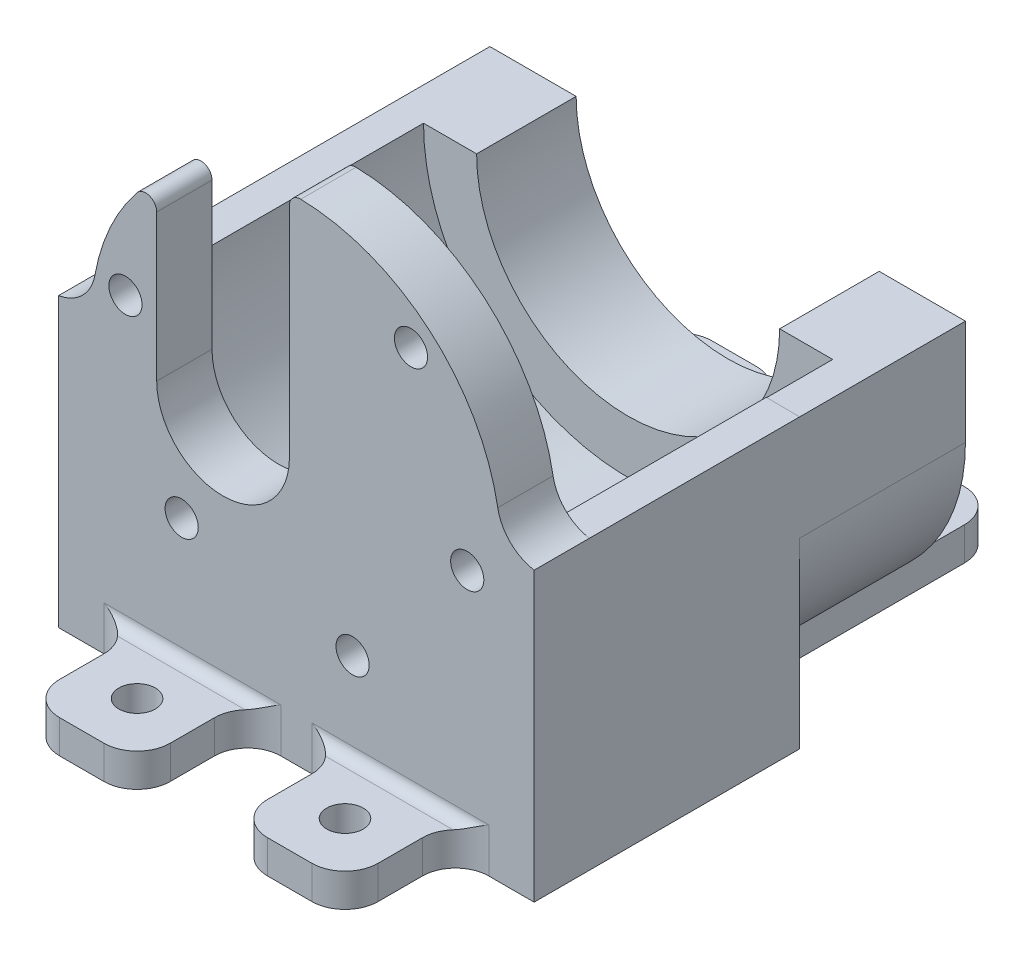
SolidWorks part; units mm, degrees
ref_plane "Front Plane" through (0, 0, 0) normal (0, 0, 1) x (1, 0, 0)
ref_plane "Top Plane" through (0, 0, 0) normal (0, 1, 0) x (1, 0, 0)
ref_plane "Right Plane" through (0, 0, 0) normal (1, 0, 0) x (0, 0, -1)
sketch "Sketch1" plane through (0, 0, 0) normal (0, 0, 1) x (1, 0, 0)
  line L0 (13.7, 13) -> (21.5, 13)
  line L3 (-21.5, 13) -> (-13.7, 13)
  line L4 (-21.5, 13) -> (-21.5, -13)
  line L5 (-21.5, -13) -> (21.5, -13)
  line L6 (21.5, 13) -> (21.5, -13)
  line L7 (-21.5, 13) -> (21.5, -13) construction
  line L8 (-21.5, -13) -> (21.5, 13) construction
  arc A0 (-13.7, 13) -> (13.7, 13) centre (0, 13) ccw
  point P0 (0, 0)
  dimension "D2" = 27.4
  dimension "D1" = 26
  dimension "43" = 43
  dimension "D3" = 7.8
  dimension "D4" = 7.8
extrude "Boss-Extrude1" add sketch "Sketch1" along normal blind 9
sketch "Sketch2" plane through (0, 0, 9) normal (0, 0, 1) x (1, 0, 0)
  line L0 (18.5, 13) -> (21.5, 13)
  line L2 (-21.5, 13) -> (-18.5, 13)
  line L3 (-21.5, 13) -> (-21.5, -13)
  line L4 (-21.5, -13) -> (21.5, -13)
  line L5 (21.5, 13) -> (21.5, -13)
  line L6 (-21.5, 13) -> (21.5, -13) construction
  line L7 (-21.5, -13) -> (21.5, 13) construction
  arc A0 (-18.5, 13) -> (18.5, 13) centre (0, 13) ccw
  point P1 (0, 0)
  dimension "D1" = 43
  dimension "37" = 37
  dimension "D2" = 26
  dimension "D3" = 3
  dimension "26" = 26
extrude "Boss-Extrude2" add sketch "Sketch2" along normal blind 25 contours L2 A0 L0 L5 L4 L3
fillet "Fillet1" radius 16.5 2 edges at (-21.5, -13, 17) (21.5, -13, 17)
sketch "Sketch4" plane through (0, 0, 0) normal (0, 0, -1) x (-1, 0, 0)
  line L0 (-21.5, 3.5) -> (-21.5, 13) construction
  line L1 (-21.5, 13) -> (-13.7, 13) construction
  line L2 (-14.4, -10) -> (-4.4, -10)
  line L3 (-14.4, -10) -> (-14.4, -13)
  line L4 (-14.4, -13) -> (-4.4, -13)
  line L5 (-4.4, -10) -> (-4.4, -13)
  line L7 (0, -15.2464) -> (0, 14.7255) construction
  line L8 (14.4, -13) -> (4.4, -13)
  line L9 (4.4, -10) -> (4.4, -13)
  line L10 (14.4, -10) -> (4.4, -10)
  line L11 (14.4, -10) -> (14.4, -13)
  dimension "D1" = 3
  dimension "10" = 10
  dimension "D2" = 17.1
  dimension "D3" = 23
extrude "Boss-Extrude3" add sketch "Sketch4" along normal blind 10 and the other way up to surface (34 mm away) other way up to face at (0, 0.9582, 34)
sketch "Sketch5" plane through (0, -10, 0) normal (0, 1, 0) x (1, 0, 0)
  line L0 (14.4, 0) -> (14.4, 10) construction
  line L2 (4.4, 10) -> (14.4, 10) construction
  line L3 (0, 16.1678) -> (0, -19.3517) construction
  circle A0 centre (9.4, 5) radius 1.65
  circle A1 centre (-9.4, 5) radius 1.65
  dimension "D1" = 3.3
  dimension "D2" = 5
  dimension "D3" = 5
extrude "Cut-Extrude1" cut sketch "Sketch5" against normal up to surface (3 mm away) up to face at (0, -13, 3.5)
fillet "Fillet2" radius 3 8 edges at (-4.4, -11.5, 0) (4.4, -11.5, 0) (9.4, -10, 0) (14.4, -11.5, -10) (4.4, -11.5, -10) (-9.4, -10, 0) (-4.4, -11.5, -10) (-14.4, -11.5, -10)
sketch "Sketch12" plane through (0, 0, 34) normal (0, 0, 1) x (1, 0, 0)
  line L0 (-14.4, -13) -> (14.4, -13) construction
  line L5 (-21.5, 13) -> (-21.5, 3.5) construction
  line L6 (-13.7, 13) -> (-18.5, 13) construction
  circle A0 centre (0, 13) radius 18.5
  circle A1 centre (0, 13) radius 15.75 construction
  circle A2 centre (-15.4519, 16.05) radius 1.5
  circle A3 centre (-5.0846, 27.9067) radius 1.5
  circle A4 centre (10.3673, 24.8567) radius 1.5
  circle A5 centre (15.4519, 9.95) radius 1.5
  circle A6 centre (5.0846, -1.9067) radius 1.5
  circle A7 centre (-10.3673, 1.1433) radius 1.5
  circle A8 centre (-6.6251, 10.74) radius 6
  dimension "D3" = 37
  dimension "D4" = 31.5
  dimension "D5" = 3
  dimension "D6" = 21.5
  dimension "D8" = 12
  dimension "D9" = 3.05
  dimension "D10" = 7
  dimension "D2" = 26
  dimension "D7" = 6
extrude "Boss-Extrude8" add sketch "Sketch12" along normal blind 5 separate body
sketch "Sketch13" plane through (0, 0, 34) normal (0, 0, 1) x (1, 0, 0)
  line L0 (-21.5, 13) -> (-18.5, 13) construction
  line L2 (-21.5, 13) -> (-21.5, -13)
  line L3 (-21.5, -13) -> (21.5, -13)
  line L4 (21.5, 13) -> (21.5, -13)
  line L5 (-18.5, 13) -> (-21.5, 13)
  line L6 (18.5, 13) -> (18.4962, 13.0344)
  line L7 (18.4962, 13.0344) -> (21.5, 13)
  arc A0 (18.5, 13) -> (-18.5, 13) centre (0, 13) cw
  arc A1 (-18.5, 13) -> (18.5, 13) centre (0, 13) ccw construction
  circle A2 centre (0, 13) radius 18.5 construction
  dimension "D1" = 26
  dimension "D2" = 43
extrude "Boss-Extrude9" add sketch "Sketch13" along normal blind 5 and the other way blind 19
sketch "Sketch14" plane through (0, -13, 0) normal (0, -1, 0) x (1, 0, 0)
  line L0 (-7.4, -10) -> (-11.4, -10)
  line L1 (7.4, -10) -> (11.4, -10)
  line L2 (-21.5, 0) -> (-21.5, 39) construction
  line L3 (-23.5178, 19.5) -> (26.295, 19.5) construction
  line L4 (7.4, 49) -> (11.4, 49)
  line L5 (-7.4, 49) -> (-11.4, 49)
  line L6 (-14.4, 46) -> (-14.4, 39)
  line L7 (-21.5, 39) -> (21.5, 39) construction
  line L8 (-4.4, 39) -> (-4.4, 46)
  line L9 (4.4, 39) -> (4.4, 46)
  line L10 (14.4, 39) -> (14.4, 46)
  line L11 (-14.4, 39) -> (-4.4, 39)
  line L12 (4.4, 39) -> (14.4, 39)
  circle A0 centre (-9.4, -5) radius 1.65
  circle A1 centre (9.4, -5) radius 1.65
  arc A2 (-14.4, -7) -> (-11.4, -10) centre (-11.4, -7) ccw
  arc A3 (-4.4, -7) -> (-7.4, -10) centre (-7.4, -7) cw
  arc A4 (7.4, -10) -> (4.4, -7) centre (7.4, -7) cw
  arc A5 (11.4, -10) -> (14.4, -7) centre (11.4, -7) ccw
  arc A6 (11.4, 49) -> (14.4, 46) centre (11.4, 46) cw
  arc A7 (7.4, 49) -> (4.4, 46) centre (7.4, 46) ccw
  arc A8 (-4.4, 46) -> (-7.4, 49) centre (-7.4, 46) ccw
  arc A9 (-14.4, 46) -> (-11.4, 49) centre (-11.4, 46) cw
  circle A10 centre (9.4, 44) radius 1.65
  circle A11 centre (-9.4, 44) radius 1.65
  dimension "D1" = 3.3
  dimension "D2" = 3.3
  dimension "D3" = 5
extrude "Boss-Extrude11" add sketch "Sketch14" against normal up to surface (3 mm away) contours L11 L8 A8 L5 A9 L6 | A11 | L12 L10 A6 L4 A7 L9 | A10 up to face at (7.75, -10, -5)
sketch "Sketch15" plane through (0, 0, 39) normal (0, 0, 1) x (1, 0, 0)
  line L0 (-12.6251, 10.74) -> (-12.6251, 26.5224)
  line L1 (-0.6251, 10.74) -> (-0.6251, 31.4894)
  arc A0 (-12.6251, 10.74) -> (-0.6251, 10.74) centre (-6.6251, 10.74) ccw
  arc A1 (-0.6251, 31.4894) -> (-12.6251, 26.5224) centre (0, 13) ccw
extrude "Cut-Extrude2" cut sketch "Sketch15" against normal blind 6
fillet "Fillet4" radius 1 4 edges at (9.4, -10, 39) (-9.4, -10, 39) (-12.6251, 26.5224, 36.5) (-0.6251, 31.4894, 36.5)
fillet "Fillet5" radius 3 6 edges at (-14.4, -11.5303, 15) (14.4, -11.5303, 15) (14.4, -11, 39) (4.4, -11, 39) (-14.4, -11, 39) (-4.4, -11, 39)
fillet "Fillet6" radius 4 2 edges at (-18.5, 13, 36.5) (18.5, 13.0344, 36.5)
